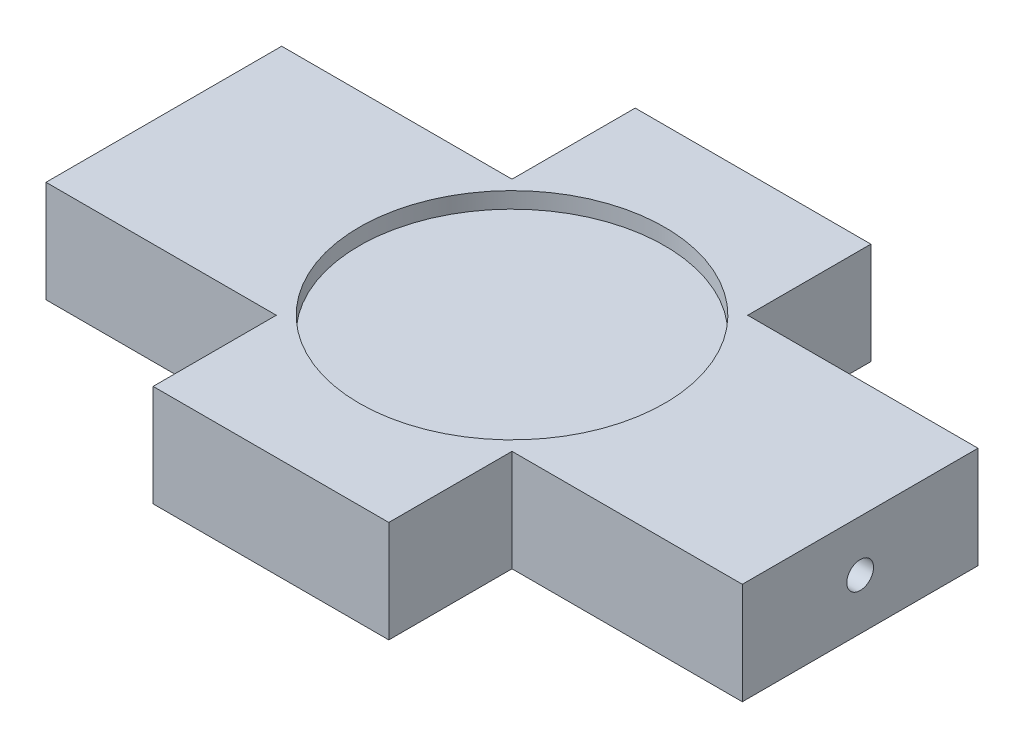
SolidWorks part; units mm, degrees
ref_plane "Front Plane" through (0, 0, 0) normal (0, 0, 1) x (1, 0, 0)
ref_plane "Top Plane" through (0, 0, 0) normal (0, 1, 0) x (1, 0, 0)
ref_plane "Right Plane" through (0, 0, 0) normal (1, 0, 0) x (0, 0, -1)
sketch "Sketch1" plane through (0, 0, 0) normal (0, 1, 0) x (1, 0, 0)
  line L1 (0, 0) -> (90, 0)
  line L2 (0, 0) -> (0, 90)
  line L3 (0, 90) -> (90, 90)
  line L4 (90, 0) -> (90, 90)
  dimension "D1" = 90
  dimension "D2" = 90
extrude "Boss-Extrude1" add sketch "Sketch1" along normal blind 19
ref_plane "Plane1" through (45, 0, 0) normal (1, 0, 0) x (0, 0, -1)
sketch "Sketch9" plane through (45, 0, 0) normal (1, 0, 0) x (0, 0, -1)
  line L0 (0, 0) -> (90, 0) construction
  line L1 (23, 19) -> (67, 19)
  line L2 (23, 19) -> (23, 0)
  line L3 (23, 0) -> (67, 0)
  line L4 (67, 19) -> (67, 0)
  line L5 (23, 19) -> (67, 0) construction
  line L6 (23, 0) -> (67, 19) construction
  line L8 (0, 19) -> (0, 0) construction
  point P0 (45, 9.5)
  dimension "D1" = 44
  dimension "D2" = 45
extrude "Boss-Extrude2" add sketch "Sketch9" along normal mid plane 130
sketch "Sketch2" plane through (0, 19, 0) normal (0, 1, 0) x (1, 0, 0)
  line L0 (45, 90) -> (45, 0) construction
  line L1 (90, 90) -> (0, 90) construction
  line L2 (0, 0) -> (90, 0) construction
  circle A0 centre (45, 45) radius 28.5
  dimension "D1" = 57
extrude "Cut-Extrude1" cut sketch "Sketch2" against normal blind 3
ref_point "Point1"
ref_axis "Axis1" through (45, 16, -45) along (0, 1, 0)
sketch "Sketch4" plane through (0, 19, 0) normal (0, 1, 0) x (1, 0, 0)
  line L1 (0, 0) -> (23, 0)
  line L2 (0, 0) -> (0, 23)
  line L3 (0, 23) -> (23, 23)
  line L4 (23, 0) -> (23, 23)
  line L5 (0, 90) -> (23, 90)
  line L6 (0, 90) -> (0, 67)
  line L7 (0, 67) -> (23, 67)
  line L8 (23, 90) -> (23, 67)
  line L9 (90, 90) -> (67, 90)
  line L10 (90, 90) -> (90, 67)
  line L11 (90, 67) -> (67, 67)
  line L12 (67, 90) -> (67, 67)
  line L13 (90, 0) -> (67, 0)
  line L14 (90, 0) -> (90, 23)
  line L15 (90, 23) -> (67, 23)
  line L16 (67, 0) -> (67, 23)
  dimension "D1" = 23
  dimension "D2" = 23
  dimension "D3" = 23
  dimension "D4" = 23
extrude "Cut-Extrude3" cut sketch "Sketch4" against normal through all
sketch "Sketch11" plane through (110, 0, 0) normal (1, 0, 0) x (0, 0, -1)
  circle A0 centre (45, 9.5) radius 2.5
  dimension "D1" = 5
extrude "Cut-Extrude4" cut sketch "Sketch11" against normal blind 10
sketch "Sketch12" plane through (-20, 0, 0) normal (-1, 0, 0) x (0, 0, 1)
  circle A0 centre (-45, 9.5) radius 2.5
extrude "Cut-Extrude5" cut sketch "Sketch12" against normal blind 10
